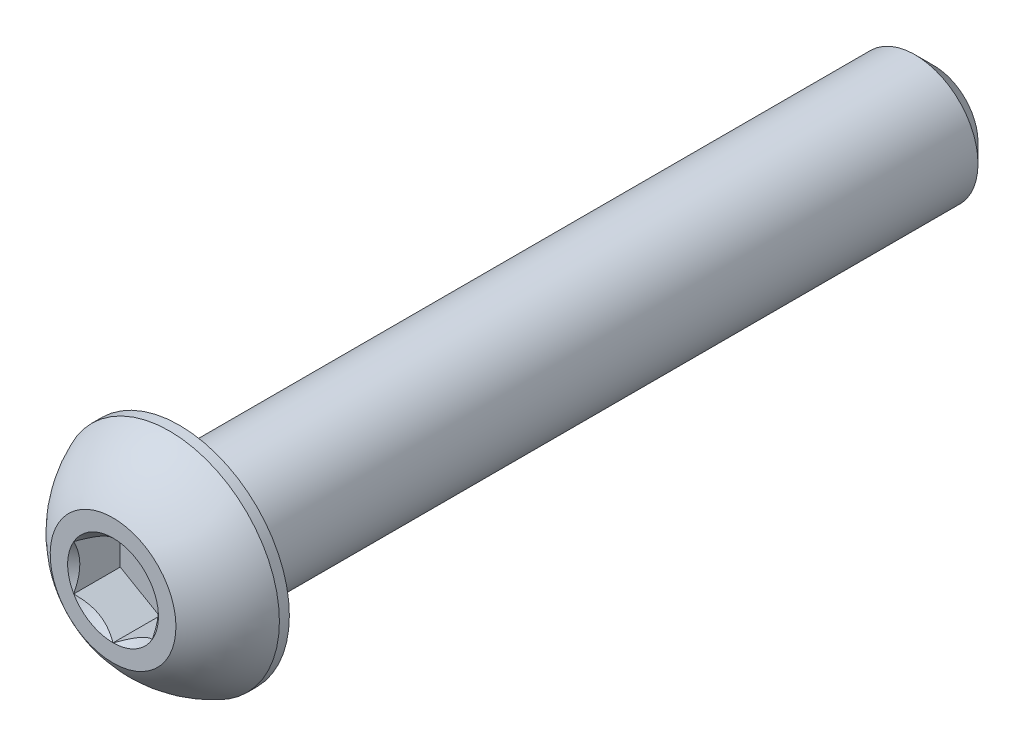
SolidWorks part; units mm, degrees
ref_plane "Front" through (0, 0, 0) normal (0, 0, 1) x (1, 0, 0)
ref_plane "Top" through (0, 0, 0) normal (0, 1, 0) x (1, 0, 0)
ref_plane "Right" through (0, 0, 0) normal (1, 0, 0) x (0, 0, -1)
sketch "Sketch1" plane through (0, 0, 0) normal (1, 0, 0) x (0, 0, -1)
  line L2 (3.3528, 3.175) -> (41.4528, 3.175)
  line L3 (41.4528, 3.175) -> (41.4528, 0)
  line L4 (41.4528, 0) -> (3.3528, 0)
  line L6 (2.8499, 5.5499) -> (3.3528, 5.5499) construction
  line L7 (41.4528, 3.175) -> (41.4528, -3.175) construction
  line L8 (0, 0) -> (3.3528, 0) construction
  line L9 (3.3528, 5.5499) -> (3.3528, -5.5499) construction
  line L11 (3.3528, 3.175) -> (3.3528, 0)
  line L13 (0, 1.9844) -> (0, -1.9844) construction
  line L14 (0, 1.9844) -> (0, 3.175) construction
  arc A3 (0, 3.175) -> (2.8499, 5.5499) centre (5.0603, 0) cw construction
  dimension "D1" = 0.5029
revolve "Revolve1" add sketch "Sketch1" angle 360 mid plane about L4
sketch "Sketch3" plane through (0, 0, -41.4528) normal (0, 0, -1) x (-1, 0, 0)
  circle A0 centre (0, 0) radius 3.175
curve "Helix/Spiral1" pitch 1.27 height 39.37 turns 31
sketch "Sketch2" plane through (0, 0, 0) normal (1, 0, 0) x (0, 0, -1)
  line L0 (41.4528, 3.175) -> (42.5641, 3.175)
  line L1 (42.5641, 3.175) -> (42.0878, 2.3501)
  line L2 (42.0878, 2.3501) -> (41.9291, 2.3501)
  line L3 (41.9291, 2.3501) -> (41.4528, 3.175)
  line L4 (41.6909, 2.7626) -> (42.3259, 2.7626) construction
  dimension "D1" = 60
  dimension "D2" = 0.1588
  dimension "D3" = 0.635
chamfer "Chamfer1" distance 0.9525 angle 45 1 edges at (0, 3.175, -41.4528)
sweep "Cut-Sweep1" [suppressed] cut profiles "Sketch2" path "Helix/Spiral1"
sketch "Sketch7" plane through (0, 0, 0) normal (1, 0, 0) x (0, 0, -1)
  line L6 (2.8499, 5.5499) -> (3.3528, 5.5499) construction
  line L8 (0, 0) -> (3.3528, 0) construction
  line L11 (3.3528, 5.5499) -> (3.3528, -5.5499) construction
  line L12 (2.8499, 5.5499) -> (3.3528, 5.5499)
  line L13 (0, 0) -> (3.3528, 0)
  line L14 (0, 1.9844) -> (0, -1.9844) construction
  line L15 (3.3528, 5.5499) -> (3.3528, 0)
  line L16 (0, 3.175) -> (0, 0)
  arc A2 (2.8499, 5.5499) -> (0, 3.175) centre (5.0603, 0) ccw construction
  arc A3 (2.8499, 5.5499) -> (0, 3.175) centre (5.0603, 0) ccw
revolve "Revolve2" add sketch "Sketch7" angle 360 mid plane about L13
sketch "Sketch5" plane through (0, 0, 0) normal (0, 0, 1) x (1, 0, 0)
  line L1 (1.9844, -1.1457) -> (1.9844, 1.1457)
  line L2 (1.9844, 1.1457) -> (0, 2.2914)
  line L3 (0, 2.2914) -> (-1.9844, 1.1457)
  line L4 (-1.9844, 1.1457) -> (-1.9844, -1.1457)
  line L5 (-1.9844, -1.1457) -> (0, -2.2914)
  line L6 (0, -2.2914) -> (1.9844, -1.1457)
  circle A0 centre (0, 0) radius 1.9844 construction
extrude "Cut-Extrude2" cut sketch "Sketch5" against normal blind 2.347
sketch "Sketch6" plane through (0, 0, 0) normal (0, 0, 1) x (1, 0, 0)
  circle A0 centre (0, 0) radius 2.2914
extrude "Cut-Extrude3" cut sketch "Sketch6" against normal blind 2.347 draft 45
sketch "Sketch9" [suppressed] plane through (0, 0, -3.3528) normal (0, 0, 1) x (1, 0, 0)
  circle A2 centre (0, 0) radius 3.175
extrude "Boss-Extrude2" [suppressed] add sketch "Sketch9" against normal offset from surface (12.7 mm away) 25.4
sketch "Sketch10" plane through (0, 0, 0) normal (1, 0, 0) x (0, 0, -1)
  line L0 (41.4528, 3.175) -> (41.4528, -3.175) construction
  point P0 (39.5478, -3.175)
  dimension "D1" = 1.905
equation "\"D3@Helix/Spiral1\" = \"Lg@Sketch1\" + \"D4@Helix/Spiral1\""
equation "\"D2@Sketch2\" = \"D4@Helix/Spiral1\" * .125"
equation "\"D3@Sketch2\" = \"D4@Helix/Spiral1\" * .5"
equation "\"D1@Chamfer1\" = \"D4@Helix/Spiral1\" * .75"
equation "\"D1@Cut-Extrude2\" = \"Head Ht@Sketch1\" * .7"
equation "\"D1@Sketch1\" = \"Head Ht@Sketch1\" * .15"
equation "\"D1@Sketch10\" = \"D4@Helix/Spiral1\" * 1.5"
equation "\"D1@Cut-Extrude3\" = \"D1@Cut-Extrude2\""
